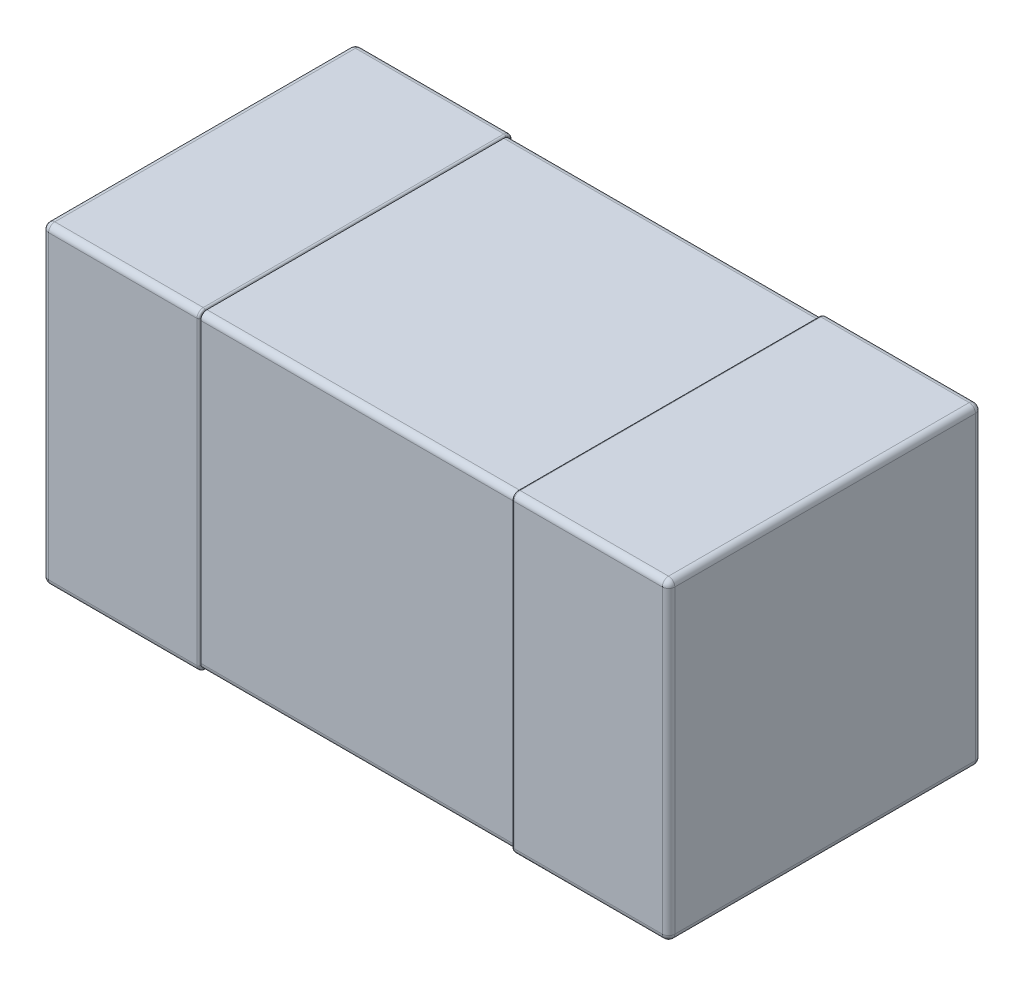
SolidWorks part; units mm, degrees
ref_plane "Top Plane" through (0, 0, 0) normal (0, 0, 1) x (1, 0, 0)
ref_plane "Front Plane" through (0, 0, 0) normal (0, 1, 0) x (1, 0, 0)
ref_plane "Side Plane" through (0, 0, 0) normal (1, 0, 0) x (0, 0, -1)
sketch "Sketch1" plane through (0, 0, 0) normal (0, 0, 1) x (1, 0, 0)
  line L1 (-0.5, 0.25) -> (0.5, 0.25)
  line L2 (-0.5, 0.25) -> (-0.5, -0.25)
  line L3 (-0.5, -0.25) -> (0.5, -0.25)
  line L4 (0.5, 0.25) -> (0.5, -0.25)
  dimension "D1" = 1
  dimension "D2" = 0.5
  dimension "D3" = 0.5
  dimension "D4" = 0.25
extrude "All body" add sketch "Sketch1" along normal blind 0.5
sketch "Sketch2" plane through (0, 0, 0) normal (1, 0, 0) x (0, 0, -1)
  line L14 (-0.003, 0.247) -> (-0.497, 0.247)
  line L15 (-0.003, -0.247) -> (-0.003, 0.247)
  line L16 (-0.497, -0.247) -> (-0.003, -0.247)
  line L17 (-0.497, 0.247) -> (-0.497, -0.247)
  line L18 (-0.003, 0.247) -> (-0.497, 0.247)
  line L19 (-0.003, -0.247) -> (-0.003, 0.247)
  line L20 (-0.497, -0.247) -> (-0.003, -0.247)
  line L21 (-0.497, 0.247) -> (-0.497, -0.247)
  dimension "D1" = 0.003
extrude "Cut out the body for pin" cut sketch "Sketch2" against normal blind 0.25 and the other way blind 0.25 flip side to cut
fillet "Body fillet" radius 0.01 4 edges at (0, 0.247, 0.003) (0, 0.247, 0.497) (0, -0.247, 0.003) (0, -0.247, 0.497)
fillet "Pin fillet a" radius 0.01 16 edges at (0.5, -0.25, 0.25) (0.5, 0, 0.5) (0.5, 0.25, 0.25) (0.5, 0, 0) (-0.5, 0.25, 0.25) (-0.5, 0, 0.5) (-0.5, -0.25, 0.25) (-0.5, 0, 0) (0.375, 0.25, 0.5) (0.375, -0.25, 0.5) (0.375, -0.25, 0) (0.375, 0.25, 0) (-0.375, 0.25, 0) (-0.375, -0.25, 0) (-0.375, 0.25, 0.5) (-0.375, -0.25, 0.5)
fillet "Pin fillet b" radius 0.003 16 edges at (0.25, -0.2471, 0.4971) (0.25, -0.25, 0.25) (0.25, -0.2471, 0.0029) (0.25, 0, 0) (0.25, 0.2471, 0.0029) (0.25, 0.25, 0.25) (0.25, 0.2471, 0.4971) (-0.25, -0.2471, 0.4971) (-0.25, -0.25, 0.25) (-0.25, -0.2471, 0.0029) (-0.25, 0, 0) (-0.25, 0.2471, 0.0029) (-0.25, 0.25, 0.25) (-0.25, 0.2471, 0.4971) (0.25, 0, 0.5) (-0.25, 0, 0.5)
